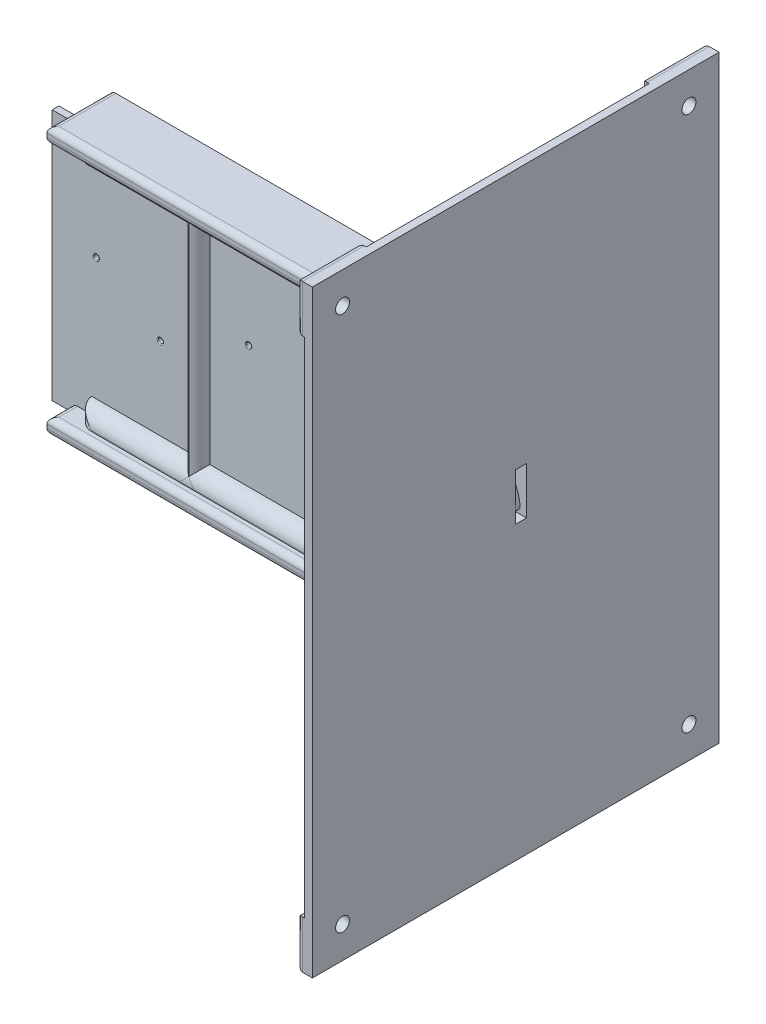
SolidWorks part; units mm, degrees
ref_plane "Front" through (0, 0, 0) normal (0, 0, 1) x (1, 0, 0)
ref_plane "Top" through (0, 0, 0) normal (0, 1, 0) x (1, 0, 0)
ref_plane "Right" through (0, 0, 0) normal (1, 0, 0) x (0, 0, -1)
sketch "Sketch1" plane through (0, 0, 0) normal (0, 0, 1) x (1, 0, 0)
  line L0 (0, 0) -> (0, 155.4998) construction
  line L1 (0, 0) -> (0, -147.6375) construction
  line L2 (0, 25.4) -> (-281.6343, 25.4) construction
  line L3 (0, -25.4) -> (-306.3875, -25.4) construction
  line L4 (-92.1, 25.4) -> (-92.1, -160.4472) construction
  line L5 (0, 25.4) -> (-92.1, 25.4)
  line L6 (-92.1, 25.4) -> (-92.1, -25.4)
  line L7 (-92.1, -25.4) -> (0, -25.4)
  line L8 (0, -25.4) -> (0, 25.4)
  point P3 (0, 25.4)
  point P5 (0, -25.4)
  point P11 (-92.1, 25.4)
  point P14 (-92.1, -25.4)
  dimension "D1" = 25.4
  dimension "W" = 25.4
  dimension "Len" = 92.1
extrude "Extrude1" add sketch "Sketch1" along normal blind 1.36
sketch "Sketch2" plane through (0, 0, 0) normal (0, 0, -1) x (-1, 0, 0)
  line L0 (0, 0) -> (98.425, 0) construction
  line L1 (0.05, 0) -> (2, 0)
  line L2 (10.2333, 10.1833) -> (10.2333, 8.2333)
  line L3 (15.35, 0) -> (15.35, 29.0677) construction
  line L4 (15.35, 15.35) -> (-21.7206, 15.35) construction
  line L5 (15.3, 15.35) -> (13.35, 15.35)
  line L6 (10.2333, 12.2333) -> (10.2333, 10.2833)
  line L7 (15.35, 15.35) -> (104.1914, 15.35) construction
  line L8 (15.4, 15.35) -> (17.35, 15.35)
  line L9 (21.8084, 4.0716) -> (20.4295, 5.4505)
  line L10 (10.53, 15.35) -> (125.7182, -99.8382) construction
  line L11 (10.53, 15.35) -> (10.53, -99.8382) construction
  line L12 (15.35, 0) -> (15.35, -83.1764) construction
  line L13 (15.35, -15.35) -> (117.3684, -15.35) construction
  line L14 (15.35, -15.35) -> (-8.0572, -15.35) construction
  line L15 (20.17, -15.35) -> (20.17, 75.8167) construction
  line L16 (20.17, -15.35) -> (-66.4064, 71.2264) construction
  line L17 (8.8916, -4.0716) -> (10.2705, -5.4505)
  line L18 (13.35, -15.35) -> (15.3, -15.35)
  line L19 (15.4, -15.35) -> (17.35, -15.35)
  line L20 (20.4667, -12.2333) -> (20.4667, -10.2833)
  line L21 (20.4667, -10.1833) -> (20.4667, -8.2333)
  line L22 (28.7, 0) -> (30.65, 0)
  line L23 (8.8916, -4.0716) -> (21.8084, 4.0716) construction
  arc A0 (0.05, 0) -> (10.2333, 10.1833) centre (10.2333, 0) cw
  arc A1 (15.3, 15.35) -> (10.2333, 10.2833) centre (10.2333, 15.35) cw
  arc A2 (2, 0) -> (10.2333, 8.2333) centre (10.2333, 0) cw
  arc A3 (10.2333, 12.2333) -> (13.35, 15.35) centre (10.2333, 15.35) ccw
  arc A4 (15.4, 15.35) -> (26.48, 15.35) centre (20.94, 15.35) cw
  arc A5 (17.35, 15.35) -> (24.53, 15.35) centre (20.94, 15.35) cw
  circle A6 centre (10.53, 15.35) radius 16 construction
  arc A7 (24.53, 15.35) -> (20.4295, 5.4505) centre (10.53, 15.35) cw
  arc A8 (26.48, 15.35) -> (21.8084, 4.0716) centre (10.53, 15.35) cw
  arc A9 (30.65, 0) -> (20.4667, -10.1833) centre (20.4667, 0) cw
  arc A10 (28.7, 0) -> (20.4667, -8.2333) centre (20.4667, 0) cw
  arc A11 (15.4, -15.35) -> (20.4667, -10.2833) centre (20.4667, -15.35) cw
  arc A12 (17.35, -15.35) -> (20.4667, -12.2333) centre (20.4667, -15.35) cw
  arc A13 (15.3, -15.35) -> (4.22, -15.35) centre (9.76, -15.35) cw
  arc A14 (13.35, -15.35) -> (6.17, -15.35) centre (9.76, -15.35) cw
  arc A15 (4.22, -15.35) -> (8.8916, -4.0716) centre (20.17, -15.35) cw
  arc A16 (6.17, -15.35) -> (10.2705, -5.4505) centre (20.17, -15.35) cw
  point P3 (30.7, 0)
  point P4 (61.4, 0)
  point P5 (92.1, 0)
  point P6 (15.35, 0)
  point P7 (46.05, 0)
  point P8 (76.75, 0)
  point P9 (10.2333, 0)
  point P10 (20.4667, 0)
  point P11 (40.9333, 0)
  point P12 (51.1667, 0)
  point P13 (71.6333, 0)
  point P14 (81.8667, 0)
  point P19 (15.35, 15.35)
  point P25 (10.2333, 15.35)
  point P31 (20.94, 15.35)
  point P38 (10.53, 15.35)
  point P50 (15.35, -15.35)
  point P54 (20.4667, -15.35)
  point P60 (9.76, -15.35)
  point P67 (20.17, -15.35)
  dimension "D11" = 10.1833
  dimension "D12" = 15.35
  dimension "D13" = 8.2333
  dimension "D14" = 5.1167
  dimension "D15" = 5.0667
  dimension "D16" = 3.1167
  dimension "D17" = 5.54
  dimension "D18" = 3.59
  dimension "D20" = 10.1833
  dimension "Dia3" = 32
  dimension "D21" = 8.2333
  dimension "D24" = 5.0667
  dimension "D25" = 3.1167
  dimension "D27" = 5.54
  dimension "D28" = 3.59
  dimension "D1" = 30.7
  dimension "pitch" = 30.7
  dimension "D2" = 15.35
  dimension "D3" = 15.35
  dimension "D4" = 15.35
  dimension "D5" = 10.2333
  dimension "D6" = 10.2333
  dimension "D7" = 10.2333
  dimension "D8" = 10.2333
  dimension "D9" = 10.2333
  dimension "D10" = 10.2333
  dimension "R2" = 5.59
  dimension "D19" = 45
  dimension "R3mR2mR2" = 4.82
  dimension "D22" = 15.35
  dimension "D23" = 5.1167
  dimension "D26" = 5.59
  dimension "D29" = 4.82
  dimension "D30" = 45
extrude "Extrude2" add sketch "Sketch2" along normal blind 1
sketch "Sketch3" plane through (0, 0, 1.36) normal (0, 0, 1) x (1, 0, 0)
  line L0 (-0.05, 0) -> (-101.6, 0) construction
  point P4 (-30.75, 0)
  point P5 (-61.45, 0)
  point P6 (-15.4, 0)
  point P7 (-46.1, 0)
  point P8 (-76.8, 0)
  point P9 (-10.2833, 0)
  point P10 (-20.5167, 0)
  point P11 (-40.9833, 0)
  point P12 (-56.3333, 0)
  point P13 (-71.6833, 0)
  point P14 (-81.9167, 0)
  point P15 (-92.15, 0)
  dimension "D1" = 30.7
  dimension "D2" = 30.7
  dimension "D3" = 15.35
  dimension "D4" = 15.35
  dimension "D5" = 15.35
  dimension "D6" = 10.2333
  dimension "D7" = 10.2333
  dimension "D8" = 10.2333
  dimension "D9" = 10.2333
  dimension "D10" = 10.2333
  dimension "D11" = 30.7
  dimension "D12" = 10.2333
fillet "Fillet1" radius 1 10 edges at (-30.65, 0, -0.5) (-10.2333, 10.1833, -0.5) (-15.3, -15.35, -0.5) (-15.4, -15.35, -0.5) (-20.4667, -10.2833, -0.5) (-20.4667, -10.1833, -0.5) (-10.2333, 10.2833, -0.5) (-15.3, 15.35, -0.5) (-15.4, 15.35, -0.5) (-0.05, 0, -0.5)
sketch "Sketch5" plane through (0, 0, 0) normal (0, 0, -1) x (-1, 0, 0)
  circle A0 centre (21.8084, 4.0716) radius 0.5
  circle A1 centre (8.8916, -4.0716) radius 0.5
  point P0 (21.8084, 4.0716)
  point P1 (8.8916, -4.0716)
extrude "Extrude3" cut sketch "Sketch5" against normal through all
fillet "Fillet2" radius 1.5 2 edges at (-21.8084, 4.0716, -0.5) (-8.8916, -4.0716, -0.5)
fillet "Fillet3" radius 0.17 4 edges at (-9.3916, -4.0716, 0) (-22.3084, 4.0716, 0) (-22.3084, 4.0716, 1.36) (-9.3916, -4.0716, 1.36)
sketch "Sketch6" plane through (0, 0, 0) normal (0, 0, -1) x (-1, 0, 0)
  line L0 (-23.8125, 0) -> (114.3, 0) construction
pattern_linear "LPattern3" count 3 spacing 30.7 along (-1, 0, 0) of "Fillet3", "Extrude3", "Extrude2", "Fillet1", "Fillet2"
sketch "Sketch7" plane through (0, 0, 0) normal (1, 0, 0) x (0, 0, -1)
  line L0 (0, 0) -> (93.6625, 0) construction
  line L1 (34.925, 0) -> (34.925, 81.1358) construction
  line L2 (34.925, 0) -> (34.925, -77.4645) construction
  line L3 (0, 0) -> (-73.025, 0) construction
  line L4 (-34.925, 0) -> (-34.925, 103.1875) construction
  line L5 (-34.925, 0) -> (-34.925, -123.825) construction
  line L6 (34.925, -53.975) -> (-138.1125, -53.975) construction
  line L7 (34.925, 53.975) -> (-80.9625, 53.975) construction
  line L8 (34.925, 60.325) -> (182.7703, 60.325) construction
  line L9 (41, 53.975) -> (41, 124.2826) construction
  line L10 (41, 53.975) -> (41, -120.7317) construction
  line L11 (34.925, -53.975) -> (109.5375, -53.975) construction
  line L12 (34.925, -60.325) -> (123.825, -60.325) construction
  line L13 (34.925, 60.325) -> (-128.5875, 60.325) construction
  line L14 (34.925, -60.325) -> (-160.5022, -60.325) construction
  line L15 (-41, -60.325) -> (-41, 84.433) construction
  line L16 (-41, 60.325) -> (41, 60.325)
  line L17 (41, 60.325) -> (41, -60.325)
  line L18 (41, -60.325) -> (-41, -60.325)
  line L19 (-41, -60.325) -> (-41, 60.325)
  line L20 (0, -1.5875) -> (2.175, -1.5875)
  line L21 (0, -8.2333) -> (0, 0) construction
  line L22 (2.175, -1.5875) -> (2.175, 7.9375)
  line L23 (2.175, 7.9375) -> (0, 7.9375)
  line L24 (0, 1.1089) -> (0, 10.1228) construction
  line L25 (0, 7.9375) -> (0, -1.5875)
  circle A0 centre (34.925, 53.975) radius 1.4
  circle A1 centre (34.925, -53.975) radius 1.4
  circle A2 centre (-34.925, -53.975) radius 1.4
  circle A3 centre (-34.925, 53.975) radius 1.4
  point P3 (34.925, 0)
  point P6 (-34.925, 0)
  point P9 (34.925, 53.975)
  point P10 (34.925, -53.975)
  point P18 (-34.925, 53.975)
  point P19 (-34.925, -53.975)
  point P20 (41, 53.975)
  point P21 (34.925, 60.325)
  point P26 (34.925, -60.325)
  point P31 (41, -60.325)
  point P32 (41, 60.325)
  point P33 (-41, -60.325)
  point P38 (-41, 60.325)
  dimension "D5" = 2.8
  dimension "HR" = 2.8
  dimension "D6" = 2.8
  dimension "D7" = 2.8
  dimension "D1" = 6.35
  dimension "HW" = 34.925
  dimension "D2" = 34.925
  dimension "D3" = 6.075
  dimension "HH" = 53.975
  dimension "D4" = 53.975
  dimension "LW" = 6.075
  dimension "LH" = 6.35
extrude "Extrude4" add sketch "Sketch7" against normal blind 3.175
sketch "Sketch8" plane through (-3.175, 0, 0) normal (-1, 0, 0) x (0, 0, 1)
  line L0 (-41, 50.7099) -> (-28.478, 50.7099)
  line L1 (-41, -60.325) -> (-41, 60.325) construction
  line L2 (-28.478, 50.7099) -> (-28.478, 60.325)
  line L3 (-41, 60.325) -> (41, 60.325) construction
  line L4 (-28.478, 60.325) -> (28.575, 60.325)
  line L5 (28.575, 60.325) -> (28.575, 50.8)
  line L6 (28.575, 50.8) -> (41, 50.8)
  line L7 (41, 60.325) -> (41, -60.325) construction
  line L8 (41, 50.8) -> (41, -50.659)
  line L9 (41, -50.659) -> (28.575, -50.659)
  line L10 (28.575, -50.659) -> (28.575, -60.325)
  line L11 (41, -60.325) -> (-41, -60.325) construction
  line L12 (28.575, -60.325) -> (-28.575, -60.325)
  line L13 (-28.575, -60.325) -> (-28.575, -50.8)
  line L14 (-28.575, -50.8) -> (-41, -50.8)
  line L15 (-41, -50.8) -> (-41, 50.7099)
  line L16 (-6.35, 26.9875) -> (6.35, 26.9875)
  line L17 (6.35, 26.9875) -> (6.35, -26.9875)
  line L18 (6.35, -26.9875) -> (-6.35, -26.9875)
  line L19 (-6.35, -26.9875) -> (-6.35, 26.9875)
extrude "Extrude5" cut sketch "Sketch8" against normal blind 1.6
fillet "Fillet4" radius 2 1 edges at (-3.175, 7.9375, -1.0875)
sketch "Sketch9" plane through (-3.175, 0, 0) normal (-1, 0, 0) x (0, 0, 1)
  line L0 (-6.35, 26.9875) -> (6.35, 26.9875)
  line L1 (6.35, 26.9875) -> (6.35, 23.8125)
  line L2 (6.35, -26.9875) -> (6.35, 26.9875) construction
  line L3 (6.35, 23.8125) -> (-6.35, 23.8125)
  line L4 (-6.35, 26.9875) -> (-6.35, -26.9875) construction
  line L5 (-6.35, 23.8125) -> (-6.35, 26.9875)
  line L6 (6.35, -26.9875) -> (6.35, -23.8125)
  line L7 (-6.35, -26.9875) -> (6.35, -26.9875) construction
  line L8 (6.35, -26.9875) -> (6.35, 26.9875) construction
  line L9 (6.35, -23.8125) -> (-6.35, -23.8125)
  line L10 (-6.35, -23.8125) -> (-6.35, -26.9875)
  line L11 (-6.35, -26.9875) -> (6.35, -26.9875)
extrude "Extrude6" add sketch "Sketch9" along normal blind 85
fillet "Fillet5" radius 1.2 31 edges at (-3.175, 55.5175, -28.478) (-3.175, 55.5625, 28.575) (-3.175, 60.325, -34.739) (-3.175, 55.5175, -41) (-3.175, 50.7099, -34.739) (-3.175, -55.5625, -41) (-3.175, -60.325, -34.7875) (-3.175, 55.5625, 41) (-3.175, 60.325, 34.7875) (-3.175, -55.492, 41) (-3.175, -60.325, 34.7875) (-3.175, -50.8, -34.7875) (-3.175, -55.5625, -28.575) (-3.175, -55.492, 28.575) (-3.175, -50.659, 34.7875) (-3.175, 50.8, 34.7875) (-3.175, 0, -6.35) (-45.675, -23.8125, -6.35) (-88.175, -23.8125, 3.855) (-88.175, -23.8125, -3.175) (-88.175, -26.9875, 0) (-45.675, 23.8125, -6.35) (-88.175, 23.8125, -3.175) (-88.175, 26.9875, 0) (-88.175, 23.8125, 3.855) (-44.875, 26.9875, 6.35) (-44.875, -26.9875, -6.35) (-44.875, -26.9875, 6.35) (-45.675, 23.8125, 6.35) (-3.175, 0, 6.35) (-45.675, -23.8125, 6.35)
sketch "Sketch10" plane through (0, 0, 1.36) normal (0, 0, 1) x (1, 0, 0)
  line L0 (-3.175, 23.8125) -> (-84.1375, 23.8125)
  line L1 (-3.175, 23.8125) -> (-86.975, 23.8125) construction
  line L2 (-84.1375, 23.8125) -> (-84.1375, 20.6375)
  line L3 (-84.1375, 20.6375) -> (-63.5, 20.6375)
  line L4 (-63.5, 20.6375) -> (-63.5, -20.6375)
  line L5 (-63.5, -20.6375) -> (-84.1375, -20.6375)
  line L6 (-84.1375, -20.6375) -> (-84.1375, -23.8125)
  line L7 (-86.975, -23.8125) -> (-3.175, -23.8125) construction
  line L8 (-84.1375, -23.8125) -> (-3.175, -23.8125)
  line L9 (-3.175, -23.8125) -> (-3.175, -20.6375)
  line L10 (-3.175, 23.8125) -> (-3.175, -23.8125) construction
  line L11 (-28.575, 20.6375) -> (-6.35, 20.6375)
  line L12 (-28.575, -20.6375) -> (-28.575, 20.6375)
  line L13 (-6.35, 20.6375) -> (-6.35, -20.6375)
  line L14 (-3.175, 20.6375) -> (-3.175, 23.8125)
  line L15 (-60.325, 20.6375) -> (-31.75, 20.6375)
  line L16 (-31.75, 20.6375) -> (-31.75, -20.6375)
  line L17 (-31.75, -20.6375) -> (-60.325, -20.6375)
  line L18 (-60.325, -20.6375) -> (-60.325, 20.6375)
  line L19 (-6.35, -20.6375) -> (-28.575, -20.6375)
  line L20 (-3.175, -20.6375) -> (-3.175, 20.6375)
extrude "Extrude7" add sketch "Sketch10" along normal blind 3
fillet "Fillet7" radius 3 13 edges at (-84.1375, -22.225, 4.36) (-73.8187, -20.6375, 4.36) (-6.35, 0, 4.36) (-17.4625, -20.6375, 4.36) (-46.0375, -20.6375, 4.36) (-17.4625, 20.6375, 4.36) (-28.575, 0, 4.36) (-31.75, 0, 4.36) (-46.0375, 20.6375, 4.36) (-60.325, 0, 4.36) (-63.5, 0, 4.36) (-73.8187, 20.6375, 4.36) (-84.1375, 22.225, 4.36)
equation "\"D1@Sketch1\" = \"W\""
equation "\"D1@Sketch2\" = \"pitch\""
equation "\"D2@Sketch2\" = \"pitch\"/2"
equation "\"D3@Sketch2\" = \"pitch\"/2"
equation "\"D4@Sketch2\" = \"pitch\"/2"
equation "\"D5@Sketch2\" = \"pitch\"/3"
equation "\"D6@Sketch2\" = \"pitch\"/3"
equation "\"D7@Sketch2\" = \"pitch\"/3"
equation "\"D8@Sketch2\" = \"pitch\"/3"
equation "\"D9@Sketch2\" = \"pitch\"/3"
equation "\"D10@Sketch2\" = \"pitch\"/3"
equation "\"D11@Sketch2\" = \"pitch\"/3-0.05"
equation "\"D13@Sketch2\" = \"pitch\"/3 -2"
equation "\"D1@Sketch3\" = \"pitch\""
equation "\"D2@Sketch3\" = \"pitch\""
equation "\"D3@Sketch3\" = \"pitch\"/2"
equation "\"D4@Sketch3\" = \"pitch\"/2"
equation "\"D5@Sketch3\" = \"pitch\"/2"
equation "\"D6@Sketch3\" = \"pitch\"/3"
equation "\"D7@Sketch3\" = \"pitch\"/3"
equation "\"D8@Sketch3\" = \"pitch\"/3"
equation "\"D9@Sketch3\" = \"pitch\"/3"
equation "\"D10@Sketch3\" = \"pitch\"/3"
equation "\"D11@Sketch3\" = \"pitch\""
equation "\"D12@Sketch3\" = \"pitch\"/3"
equation "\"D12@Sketch2\" = \"pitch\"/2"
equation "\"D14@Sketch2\" = \"pitch\"/6"
equation "\"D15@Sketch2\" = \"pitch\"/6-0.05"
equation "\"D16@Sketch2\" = \"pitch\"/6-2"
equation "\"D17@Sketch2\" = \"R2\"-0.05"
equation "\"D18@Sketch2\" = \"R2\"-2"
equation "\"D20@Sketch2\" = \"pitch\"/3-0.05"
equation "\"D21@Sketch2\" = \"pitch\"/3-2"
equation "\"D22@Sketch2\" = \"pitch\"/2"
equation "\"D23@Sketch2\" = \"pitch\"/6"
equation "\"D24@Sketch2\" = \"pitch\"/6-0.05"
equation "\"D25@Sketch2\" = \"pitch\"/6-2"
equation "\"D26@Sketch2\" = \"R2\""
equation "\"D27@Sketch2\" = \"R2\"-0.05"
equation "\"D28@Sketch2\" = \"R2\"-2"
equation "\"D29@Sketch2\" = \"R3mR2mR2\""
equation "\"D2@Sketch7\" = \"HW\""
equation "\"D4@Sketch7\" = \"HH\""
equation "\"D1@Sketch7\" = \"LH\""
equation "\"D3@Sketch7\" = \"LW\""
equation "\"D5@Sketch7\" = \"HR\""
equation "\"D6@Sketch7\" = \"HR\""
equation "\"D7@Sketch7\" = \"HR\""
